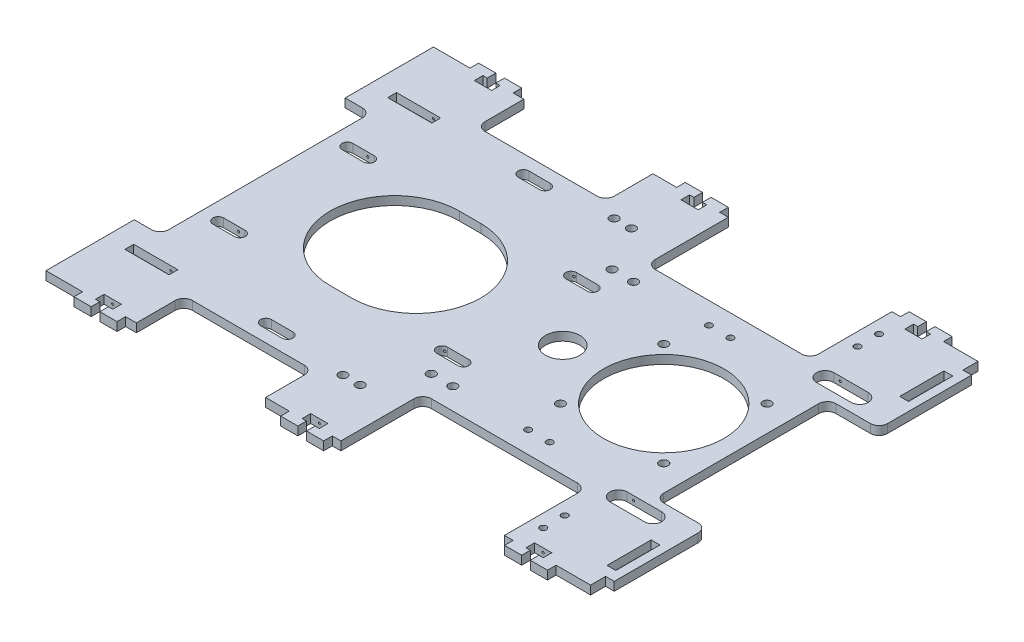
SolidWorks part; units mm, degrees
material "Ст 3 ГОСТ 380-88"
ref_plane "Спереди" through (0, 0, 0) normal (0, 0, 1) x (1, 0, 0)
ref_plane "Сверху" through (0, 0, 0) normal (0, 1, 0) x (1, 0, 0)
ref_plane "Справа" through (0, 0, 0) normal (1, 0, 0) x (0, 0, -1)
other "Configuration Table"
sketch "Эскиз1" plane through (0, 0, 0) normal (0, 1, 0) x (1, 0, 0)
  line L0 (0, -90) -> (290, -90) construction
  line L1 (0, 0) -> (17, 0)
  line L2 (0, 0) -> (0, -41)
  line L4 (257, -7) -> (257, -46)
  line L5 (37, 0) -> (42, 0)
  line L7 (17, 0) -> (17, 4)
  line L8 (17, 4) -> (25, 4)
  line L9 (37, 0) -> (37, 4)
  line L10 (29, 0) -> (31, 0)
  line L12 (25, 4) -> (25, 0)
  line L14 (29, 4) -> (29, 0)
  line L15 (23, 0) -> (25, 0)
  line L16 (23, 0) -> (23, -4)
  line L17 (23, -4) -> (31, -4)
  line L18 (31, 0) -> (31, -4)
  line L19 (29, 4) -> (37, 4)
  line L20 (20.0385, -120) -> (30.0385, -120) construction
  line L61 (9.75, -26.9) -> (30.25, -26.9)
  line L62 (9.75, -26.9) -> (9.75, -31)
  line L63 (9.75, -31) -> (30.25, -31)
  line L64 (30.25, -26.9) -> (30.25, -31)
  line L68 (133, 0) -> (137, 0)
  line L70 (113, 0) -> (113, 4)
  line L71 (113, 4) -> (121, 4)
  line L72 (133, 0) -> (133, 4)
  line L73 (125, 0) -> (127, 0)
  line L75 (121, 4) -> (121, 0)
  line L77 (125, 4) -> (125, 0)
  line L78 (119, 0) -> (121, 0)
  line L79 (119, 0) -> (119, -4)
  line L80 (119, -4) -> (127, -4)
  line L81 (127, 0) -> (127, -4)
  line L82 (125, 4) -> (133, 4)
  line L96 (72, -90) -> (82, -90) construction
  line L97 (72, -60) -> (82, -60)
  line L99 (77, -90) -> (18.6203, -56.2945) construction
  line L100 (77, -154.4519) -> (77, -25.5481) construction
  line L101 (20.0385, -60) -> (30.0385, -60) construction
  line L102 (20.0385, -57.5) -> (30.0385, -57.5)
  line L103 (20.0385, -62.5) -> (30.0385, -62.5)
  line L104 (133.9615, -59.9967) -> (123.9615, -60.0033) construction
  line L105 (133.9599, -57.4967) -> (123.9599, -57.5033)
  line L106 (133.9632, -62.4967) -> (123.9632, -62.5033)
  line L107 (20.0385, -122.5) -> (30.0385, -122.5)
  line L110 (20.0385, -117.5) -> (30.0385, -117.5)
  line L113 (82, -30.2087) -> (72, -30.2087) construction
  line L114 (82, -32.7087) -> (72, -32.7087)
  line L115 (82, -27.7087) -> (72, -27.7087)
  line L116 (133.9615, -120.0033) -> (123.9615, -119.9967) construction
  line L128 (237, -50) -> (253, -50)
  line L129 (233, -54) -> (233, -126)
  line L132 (224, -42) -> (240, -42) construction
  line L133 (224, -38) -> (240, -38)
  line L134 (224, -46) -> (240, -46)
  line L135 (133.9599, -122.5033) -> (123.9599, -122.4967)
  line L139 (248.9, -11.75) -> (253, -11.75)
  line L140 (248.9, -11.75) -> (248.9, -32.25)
  line L141 (248.9, -32.25) -> (253, -32.25)
  line L142 (253, -11.75) -> (253, -32.25)
  line L149 (46, -22) -> (98, -22)
  line L150 (102, 0) -> (102, -18)
  line L171 (42, -18) -> (42, 0)
  line L172 (102, 0) -> (113, 0)
  line L173 (237, 0) -> (237, 4)
  line L174 (237, 4) -> (229, 4)
  line L175 (229, 4) -> (229, 0)
  line L176 (229, 0) -> (231, 0)
  line L177 (231, 0) -> (231, -4)
  line L178 (231, -4) -> (223, -4)
  line L179 (225, 4) -> (225, 0)
  line L180 (223, 0) -> (225, 0)
  line L181 (223, 0) -> (223, -4)
  line L182 (225, 4) -> (217, 4)
  line L183 (217, 0) -> (217, 4)
  line L184 (237, 0) -> (253, 0)
  line L185 (213, 0) -> (217, 0)
  line L187 (137, 0) -> (137, -34)
  line L188 (141, -38) -> (209, -38)
  line L189 (213, 0) -> (213, -34)
  line L198 (77, -90) -> (128.9615, -60) construction
  line L199 (133.9632, -117.5033) -> (123.9632, -117.4967)
  line L200 (82, -149.7913) -> (72, -149.7913) construction
  line L201 (82, -147.2913) -> (72, -147.2913)
  line L206 (82, -152.2913) -> (72, -152.2913)
  line L207 (224, -138) -> (240, -138) construction
  line L208 (123, -208.83) -> (123, 28.83) construction
  line L209 (224, -142) -> (240, -142)
  line L210 (224, -134) -> (240, -134)
  line L211 (77, -90) -> (128.9615, -120) construction
  line L212 (77, -90) -> (18.6203, -123.7055) construction
  line L213 (213, -180) -> (213, -146)
  line L214 (141, -142) -> (209, -142)
  line L215 (137, -180) -> (137, -146)
  line L216 (213, -180) -> (217, -180)
  line L217 (237, -180) -> (253, -180)
  line L218 (217, -180) -> (217, -184)
  line L219 (225, -184) -> (217, -184)
  line L220 (223, -180) -> (223, -176)
  line L221 (223, -180) -> (225, -180)
  line L222 (225, -184) -> (225, -180)
  line L223 (231, -176) -> (223, -176)
  line L224 (231, -180) -> (231, -176)
  line L225 (229, -180) -> (231, -180)
  line L226 (229, -184) -> (229, -180)
  line L227 (237, -184) -> (229, -184)
  line L228 (237, -180) -> (237, -184)
  line L229 (102, -180) -> (113, -180)
  line L230 (42, -162) -> (42, -180)
  line L231 (102, -180) -> (102, -162)
  line L232 (46, -158) -> (98, -158)
  line L233 (253, -168.25) -> (253, -147.75)
  line L234 (248.9, -147.75) -> (253, -147.75)
  line L235 (248.9, -168.25) -> (248.9, -147.75)
  line L236 (248.9, -168.25) -> (253, -168.25)
  line L237 (237, -130) -> (253, -130)
  line L242 (72, -120) -> (82, -120)
  line L243 (125, -184) -> (133, -184)
  line L244 (127, -180) -> (127, -176)
  line L245 (119, -176) -> (127, -176)
  line L246 (119, -180) -> (119, -176)
  line L247 (119, -180) -> (121, -180)
  line L248 (125, -184) -> (125, -180)
  line L249 (121, -184) -> (121, -180)
  line L250 (125, -180) -> (127, -180)
  line L251 (133, -180) -> (133, -184)
  line L252 (113, -184) -> (121, -184)
  line L253 (113, -180) -> (113, -184)
  line L254 (133, -180) -> (137, -180)
  line L255 (30.25, -153.1) -> (30.25, -149)
  line L256 (9.75, -149) -> (30.25, -149)
  line L257 (9.75, -153.1) -> (9.75, -149)
  line L258 (9.75, -153.1) -> (30.25, -153.1)
  line L259 (29, -184) -> (37, -184)
  line L260 (31, -180) -> (31, -176)
  line L261 (23, -176) -> (31, -176)
  line L262 (23, -180) -> (23, -176)
  line L263 (23, -180) -> (25, -180)
  line L264 (29, -184) -> (29, -180)
  line L265 (25, -184) -> (25, -180)
  line L266 (29, -180) -> (31, -180)
  line L267 (37, -180) -> (37, -184)
  line L268 (17, -184) -> (25, -184)
  line L269 (17, -180) -> (17, -184)
  line L270 (37, -180) -> (42, -180)
  line L271 (257, -173) -> (257, -134)
  line L272 (0, -180) -> (0, -139)
  line L273 (0, -180) -> (17, -180)
  line L275 (0, -41) -> (8, -41)
  line L277 (0, -139) -> (8, -139)
  line L278 (12, -45) -> (12, -135)
  line L281 (257, -7) -> (253, -7)
  line L282 (253, 0) -> (253, -7)
  line L285 (257, -173) -> (253, -173)
  line L286 (253, -180) -> (253, -173)
  arc A0 (72, -60) -> (72, -120) centre (72, -90) ccw
  arc A1 (82, -120) -> (82, -60) centre (82, -90) ccw
  arc A3 (20.0385, -57.5) -> (20.0385, -62.5) centre (20.0385, -60) ccw
  arc A4 (30.0385, -62.5) -> (30.0385, -57.5) centre (30.0385, -60) ccw
  arc A5 (133.9599, -57.4967) -> (133.9632, -62.4967) centre (133.9615, -59.9967) cw
  arc A6 (123.9632, -62.5033) -> (123.9599, -57.5033) centre (123.9615, -60.0033) cw
  arc A11 (82, -32.7087) -> (82, -27.7087) centre (82, -30.2087) ccw
  arc A12 (72, -27.7087) -> (72, -32.7087) centre (72, -30.2087) ccw
  circle A15 centre (197, -90) radius 28
  circle A16 centre (173, -66) radius 2
  circle A17 centre (221, -66) radius 2
  arc A28 (237, -50) -> (233, -54) centre (237, -54) ccw
  arc A31 (253, -50) -> (257, -46) centre (253, -46) ccw
  arc A32 (224, -38) -> (224, -46) centre (224, -42) ccw
  arc A33 (240, -46) -> (240, -38) centre (240, -42) ccw
  arc A40 (42, -18) -> (46, -22) centre (46, -18) ccw
  arc A41 (98, -22) -> (102, -18) centre (98, -18) ccw
  circle A46 centre (140.9852, -48) radius 2
  circle A47 centre (130.9852, -48) radius 2
  circle A50 centre (118.9615, -27) radius 2
  circle A51 centre (110.9615, -27) radius 2
  arc A52 (209, -38) -> (213, -34) centre (209, -34) ccw
  arc A53 (137, -34) -> (141, -38) centre (141, -34) ccw
  arc A62 (20.0385, -122.5) -> (20.0385, -117.5) centre (20.0385, -120) cw
  circle A63 centre (77, -90) radius 60 construction
  arc A64 (30.0385, -117.5) -> (30.0385, -122.5) centre (30.0385, -120) cw
  circle A65 centre (221, -114) radius 2 [skipped]
  circle A66 centre (173, -114) radius 2 [skipped]
  arc A67 (133.9599, -122.5033) -> (133.9632, -117.5033) centre (133.9615, -120.0033) ccw
  arc A68 (123.9632, -117.4967) -> (123.9599, -122.4967) centre (123.9615, -119.9967) ccw
  arc A69 (82, -147.2913) -> (82, -152.2913) centre (82, -149.7913) cw
  arc A70 (72, -152.2913) -> (72, -147.2913) centre (72, -149.7913) cw
  arc A71 (224, -142) -> (224, -134) centre (224, -138) cw
  arc A72 (240, -134) -> (240, -142) centre (240, -138) cw
  arc A73 (137, -146) -> (141, -142) centre (141, -146) cw
  arc A74 (209, -142) -> (213, -146) centre (209, -146) cw
  circle A75 centre (110.9615, -153) radius 2
  circle A76 centre (118.9615, -153) radius 2
  circle A77 centre (130.9852, -132) radius 2
  circle A78 centre (140.9852, -132) radius 2
  arc A79 (98, -158) -> (102, -162) centre (98, -162) cw
  arc A80 (42, -162) -> (46, -158) centre (46, -162) cw
  arc A81 (253, -130) -> (257, -134) centre (253, -134) cw
  arc A82 (237, -130) -> (233, -126) centre (237, -126) cw
  circle A87 centre (221, -114) radius 2
  circle A88 centre (173, -114) radius 2
  circle A89 centre (150.0624, -90) radius 8
  arc A90 (8, -41) -> (12, -45) centre (8, -45) cw
  arc A91 (8, -139) -> (12, -135) centre (8, -135) ccw
  circle A92 centre (219, -12) radius 1.5
  circle A93 centre (219, -22) radius 1.5
  circle A94 centre (219, -158) radius 1.5
  circle A95 centre (219, -168) radius 1.5
  circle A96 centre (176, -132) radius 1.5
  circle A97 centre (186, -132) radius 1.5
  circle A98 centre (186, -48) radius 1.5
  circle A99 centre (176, -48) radius 1.5
  point P33 (25.0385, -120)
  point P40 (128.9615, -120)
  point P47 (77, -149.7913)
  point P54 (232, -138)
  point P70 (123, -90)
  point P77 (121, 2)
  point P92 (77, -90)
  point P103 (25.0385, -60)
  point P108 (77, -30.2087)
  point P113 (128.9615, -60)
  point P195 (232, -42)
  point P225 (137, -38)
  point P226 (233, -90)
  point P238 (39.9992, -22)
  point P241 (102, -22)
  point P294 (102, -158)
  point P295 (39.9992, -158)
  point P296 (137, -142)
  dimension "D28" = 30
  dimension "D33" = 56
  dimension "D35" = 4
  dimension "D38" = 2
  dimension "D44" = 6
  dimension "D48" = 4
  dimension "D61" = 8
  dimension "D64" = 3
  dimension "D65" = 7
  dimension "D66" = 7
  dimension "D70" = 186
  dimension "D68" = 3
  dimension "D60" = 4
  dimension "D16" = 16
  dimension "D46" = 4
  dimension "D47" = 4
  dimension "D42" = 3
  dimension "D67" = 3
  dimension "D3" = 17
  dimension "D4" = 20
  dimension "D5" = 4
  dimension "D6" = 8
  dimension "D7" = 4
  dimension "D8" = 4
  dimension "D9" = 2
  dimension "D10" = 2
  dimension "D11" = 4.1
  dimension "D12" = 35
  dimension "D13" = 20.5
  dimension "D14" = 9.75
  dimension "D15" = 20
  dimension "D17" = 10
  dimension "D18" = 4
  dimension "D19" = 4
  dimension "D20" = 8
  dimension "D21" = 4
  dimension "D22" = 4
  dimension "D23" = 2
  dimension "D24" = 2
  dimension "D25" = 10
  dimension "D26" = 10
  dimension "D27" = 12
  dimension "D29" = 5
  dimension "D30" = 10
  dimension "D31" = 5
  dimension "D32" = 10
  dimension "D34" = 60
  dimension "D36" = 24
  dimension "D37" = 24
  dimension "D40" = 48
  dimension "D41" = 10
  dimension "D43" = 10
  dimension "D45" = 38
  dimension "D49" = 8
  dimension "D50" = 16
  dimension "D51" = 76
  dimension "D52" = 25
  dimension "D53" = 20.5
  dimension "D54" = 4.1
  dimension "D55" = 4
  dimension "D56" = 44
  dimension "D57" = 22
  dimension "D58" = 42
  dimension "D59" = 60
  dimension "D62" = 40
  dimension "D63" = 24
  dimension "D69" = 10
  dimension "D73" = 2
  dimension "D74" = 2
  dimension "D75" = 4
  dimension "D76" = 4
  dimension "D77" = 4
  dimension "D87" = 20
  dimension "D88" = 90
  dimension "D90" = 11.75
  dimension "D93" = 60
  dimension "D94" = 10
  dimension "D96" = 60
  dimension "D97" = 30
  dimension "D39" = 2
base flange "Базовая кромка1" sketch "Эскиз1" thickness 4 reverse thickness direction no parameters "D1"=0.7366
sketch "Эскиз2" plane through (0, 0, 176) normal (0, 0, 1) x (1, 0, 0)
  line L0 (223, 0) -> (231, 0) construction
  line L1 (225, -4) -> (225, 0) construction
  line L2 (121, -4) -> (121, 0) construction
  line L3 (25, -4) -> (25, 0) construction
  circle A0 centre (27, -2) radius 0.5
  circle A1 centre (123, -2) radius 0.5
  circle A2 centre (227, -2) radius 0.5
  dimension "D1" = 1
  dimension "D2" = 2
  dimension "D3" = 2
  dimension "D4" = 2
  dimension "D5" = 2
extrude "Вырез-Вытянуть1" cut sketch "Эскиз2" against normal through all normal cut yes
sketch "Сгиб-Линии1" [suppressed] plane through (0, 0, 0) normal (0, 1, 0) x (1, 0, 0)
sketch "Граничная рамка1" [suppressed] plane through (0, 0, 0) normal (0, 1, 0) x (1, 0, 0)
sheet metal parameters "Листовой металл3" thickness 4 parameters "D1"=0.7366
flat pattern "Развертка3" [suppressed]
sketch "Сгиб-Линии2" plane through (0, 0, 0) normal (0, 1, 0) x (1, 0, 0)
sketch3d "Граничная рамка2" [suppressed]
  line L0 (290, -172, 0) -> (0, -172, 0) construction
  line L1 (290, 4, 0) -> (0, 4, 0) construction
  line L2 (290, -172, 0) -> (290, 4, 0) construction
  line L3 (0, -172, 0) -> (0, 4, 0) construction
sheet metal parameters "Листовой металл6" thickness 4 parameters "D1"=0.7366
flat pattern "Развертка3"
sketch "Сгиб-Линии2" plane through (0, 0, 0) normal (0, 1, 0) x (1, 0, 0)
sketch3d "Граничная рамка2" [suppressed]
  line L0 (249, 49, 0) -> (-8, 49, 0) construction
  line L1 (249, -139, 0) -> (-8, -139, 0) construction
  line L2 (249, 49, 0) -> (249, -139, 0) construction
  line L3 (-8, 49, 0) -> (-8, -139, 0) construction
